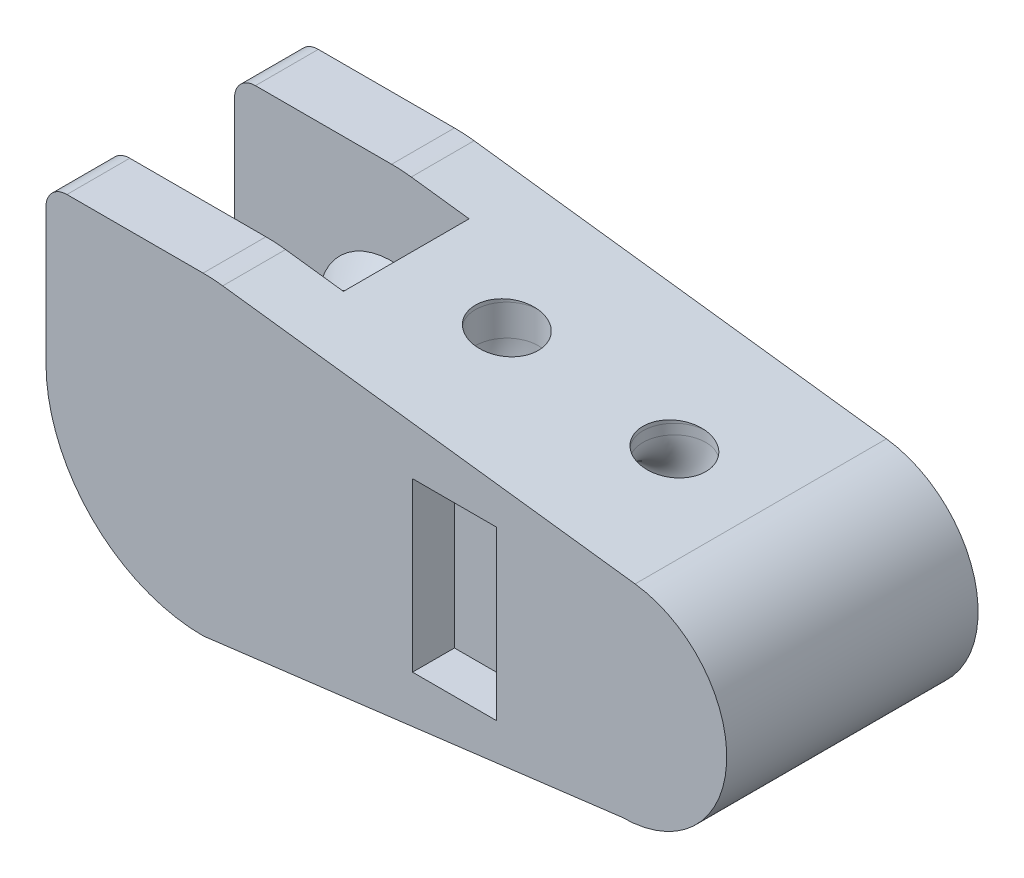
SolidWorks part; units mm, degrees
ref_plane "Front Plane" through (0, 0, 0) normal (0, 0, 1) x (1, 0, 0)
ref_plane "Top Plane" through (0, 0, 0) normal (0, 1, 0) x (1, 0, 0)
ref_plane "Right Plane" through (0, 0, 0) normal (1, 0, 0) x (0, 0, -1)
sketch "Sketch1" plane through (0, 0, 0) normal (0, 0, 1) x (1, 0, 0)
  line L0 (55, 0) -> (-55, 0) construction
  line L1 (0, -55) -> (0, 55) construction
  line L2 (-9.0625, 7.4412) -> (10.625, 4.9608)
  line L3 (-10, -7.5) -> (10, -5)
  line L4 (-10, 7.5) -> (-16.5, 7.5)
  line L5 (-17.5, 6.5) -> (-17.5, 0)
  arc A0 (-17.5, 0) -> (-10, 7.5) centre (-10, 0) ccw
  circle A1 centre (10, 0) radius 5
  circle A2 centre (-10, 0) radius 2.5
  arc A4 (-17.5, 6.5) -> (-16.5, 7.5) centre (-16.5, 6.5) cw
  dimension "D1" = 15
  dimension "D2" = 10
  dimension "D5" = 5
  dimension "D7" = 1
  dimension "D3" = 20
  dimension "D4" = 10
extrude "Boss-Extrude1" add sketch "Sketch1" along normal mid plane 12 contours A1 L2 A0 L3 region at (1.0148, 0.0458, 0)
extrude "Boss-Extrude2" add sketch "Sketch1<3>" along normal mid plane 12 contours A0 L3 A2 region at (-2.726, 0.4493, 0)
sketch "Sketch1<3>" plane through (0, 0, 0) normal (0, 0, 1) x (1, 0, 0) same geometry as "Sketch1"
extrude "Boss-Extrude3" add sketch "Sketch1<5>" along normal mid plane 12 contours A1 region at (10, 0, 0)
sketch "Sketch1<5>" plane through (0, 0, 0) normal (0, 0, 1) x (1, 0, 0) same geometry as "Sketch1"
sketch "Sketch2" plane through (0, 0, 0) normal (0, 0, 1) x (1, 0, 0)
  line L0 (-2, 0) -> (-2, -8)
  line L1 (-2, -8) -> (-10, -8)
  line L8 (-18, 0) -> (-18, 8.1082)
  line L9 (-18, 8.1082) -> (-10, 8)
  arc A0 (-2, 0) -> (-10, 8) centre (-10, 0) ccw
  arc A2 (-18, 0) -> (-10, -8) centre (-10, 0) ccw
  dimension "D1" = 16
extrude "Cut-Extrude3" cut sketch "Sketch2" against normal mid plane 6 contours L0 A0 L1 region at (-10.0101, 0.0152, 0)
sketch "Sketch3" plane through (0, 0, 0) normal (0, 0, 1) x (1, 0, 0)
  line L0 (-1.5, 6.4884) -> (-1.5, 5)
  line L2 (1.5, 2) -> (3.5, 2)
  line L3 (6.5, 5) -> (6.5, 5.4805)
  line L4 (-9.0625, 7.4412) -> (10.625, 4.9608) construction
  line L5 (-1.5, 6.4884) -> (-1.5, 8.192)
  line L6 (6.5, 5.4805) -> (6.5, 8.192)
  line L8 (0, -6.6) -> (0, 6.6) construction
  line L9 (6.6, 0) -> (-6.6, 0) construction
  arc A2 (6.5, 5) -> (3.5, 2) centre (3.5, 5) cw
  arc A3 (1.5, 2) -> (-1.5, 5) centre (1.5, 5) cw
  point P24 (6.5, 2)
  point P27 (-1.5, 2)
  dimension "D1" = 8
  dimension "D2" = 1.5
  dimension "D3" = 2
sweep "Cut-Sweep5" cut path "Sketch3" circular profile diameter 3 parameters "D3"=3
mirror "Mirror4" about plane through (0, 0, 0) normal (0, 1, 0) of "Cut-Sweep5"
extrude "Boss-Extrude4" add sketch "Sketch1<7>" along normal mid plane 12 contours A2 region at (-10, 0, 0)
sketch "Sketch1<7>" plane through (0, 0, 0) normal (0, 0, 1) x (1, 0, 0) same geometry as "Sketch1"
chamfer "Chamfer1" distance 1 angle 45 2 edges at (-7.5, 0, 3) (-7.5, 0, -3)
sketch "Sketch130" plane through (0, 0, 0) normal (0, 1, 0) x (1, 0, 0)
  line L0 (0, -6) -> (0, -4)
  line L1 (0, -6.6) -> (0, 6.6) construction
  line L2 (-9.0625, -6) -> (10.625, -6) construction
  line L3 (0, -4) -> (3, -4)
  line L4 (3, -4) -> (4, -6)
  line L5 (4, -6) -> (4, -8.476)
  line L6 (4, -8.476) -> (0, -8.476)
  line L7 (0, -8.476) -> (0, -6)
  dimension "D1" = 2
  dimension "D2" = 1
  dimension "D3" = 3
extrude "Cut-Extrude4" cut sketch "Sketch130" against normal mid plane 8
mirror "Mirror5" about plane through (0, 0, 0) normal (0, 0, 1) of "Cut-Extrude4"
